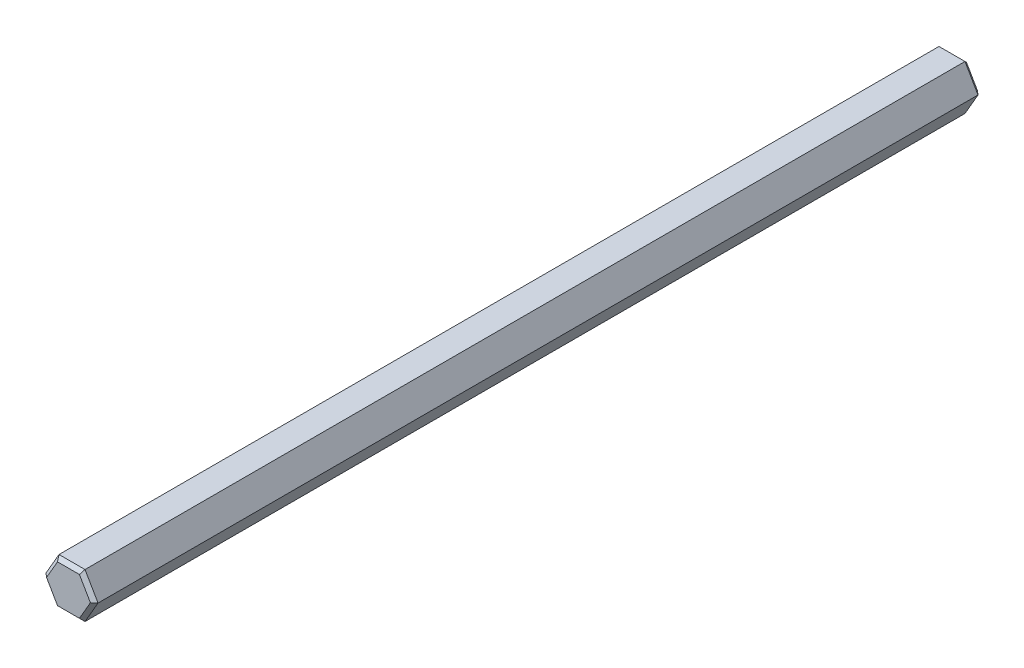
SolidWorks part; units mm, degrees
ref_plane "Front Plane" through (0, 0, 0) normal (0, 0, 1) x (1, 0, 0)
ref_plane "Top Plane" through (0, 0, 0) normal (0, 1, 0) x (1, 0, 0)
ref_plane "Right Plane" through (0, 0, 0) normal (1, 0, 0) x (0, 0, -1)
sketch "Sketch1" plane through (0, 0, 0) normal (0, 0, 1) x (1, 0, 0)
  line L1 (3.6662, 0) -> (1.8331, 3.175)
  line L2 (1.8331, 3.175) -> (-1.8331, 3.175)
  line L3 (-1.8331, 3.175) -> (-3.6662, 0)
  line L4 (-3.6662, 0) -> (-1.8331, -3.175)
  line L5 (-1.8331, -3.175) -> (1.8331, -3.175)
  line L6 (1.8331, -3.175) -> (3.6662, 0)
  circle A0 centre (0, 0) radius 3.175 construction
  dimension "D1" = 6.35
extrude "Boss-Extrude1" add sketch "Sketch1" along normal mid plane 125
ref_axis "Axis1" through (0, 0, -41.25) along (0, 0, 1)
chamfer "Chamfer1" distance 0.5 angle 45 12 edges at (2.7496, 1.5875, -62.5) (0, 3.175, -62.5) (-2.7496, 1.5875, -62.5) (-2.7496, -1.5875, -62.5) (0, -3.175, -62.5) (2.7496, -1.5875, -62.5) (0, -3.175, 62.5) (-2.7496, -1.5875, 62.5) (-2.7496, 1.5875, 62.5) (0, 3.175, 62.5) (2.7496, 1.5875, 62.5) (2.7496, -1.5875, 62.5)
